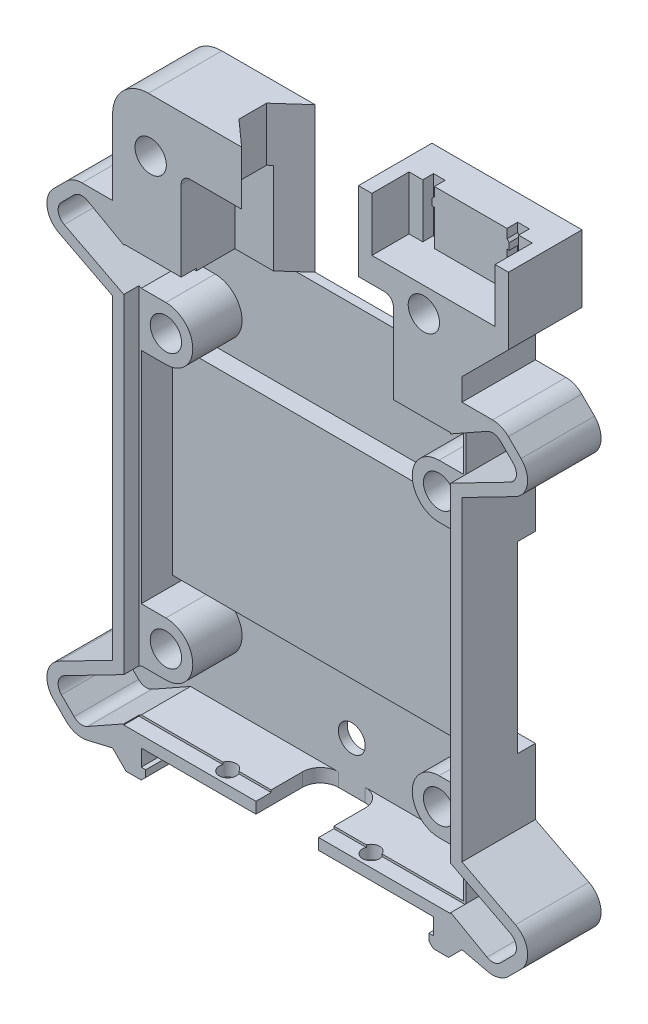
SolidWorks part; units mm, degrees
ref_plane "Front Plane" through (0, 0, 0) normal (0, 0, 1) x (1, 0, 0)
ref_plane "Top Plane" through (0, 0, 0) normal (0, 1, 0) x (1, 0, 0)
ref_plane "Right Plane" through (0, 0, 0) normal (1, 0, 0) x (0, 0, -1)
sketch "Sketch1" plane through (0, 0, 0) normal (0, 0, 1) x (1, 0, 0)
  line L0 (15.25, -20.35) -> (18, -20.35)
  line L1 (-19.5, -32.6) -> (19.5, -32.6)
  line L2 (-19.5, -32.6) -> (-19.5, 31.1)
  line L3 (-19.5, 31.1) -> (19.5, 31.1)
  line L4 (19.5, -32.6) -> (19.5, 31.1)
  line L5 (-15.25, -20.35) -> (-18, -20.35)
  line L6 (15.25, -26.35) -> (18, -26.35)
  line L7 (6.95, 31.1) -> (-15.5, 31.1) construction
  line L8 (-18, -31.1) -> (-18, 29.6)
  line L9 (-18, 29.6) -> (18, 29.6)
  line L10 (18, -31.1) -> (18, 29.6)
  line L11 (-18, -31.1) -> (18, -31.1)
  line L12 (-18, 14.9) -> (18, 14.9)
  line L13 (7.85, 14.9) -> (-4.95, 14.9) construction
  line L14 (-15.25, 4.15) -> (-18, 4.15)
  line L15 (-15.25, 10.15) -> (-18, 10.15)
  line L16 (15.25, 10.15) -> (18, 10.15)
  line L17 (15.25, 4.15) -> (18, 4.15)
  line L18 (-15.25, -26.35) -> (-18, -26.35)
  line L19 (19.5, -32.6) -> (19.5, -18.35) construction
  line L20 (-19.5, -32.6) -> (-19.5, -18.35) construction
  line L21 (19.5, -32.6) -> (-19.5, -32.6) construction
  line L22 (0, 31.1) -> (0, -32.6) construction
  line L23 (9.45, 26.9) -> (24.7, 26.9)
  line L24 (9.45, 26.9) -> (9.45, 33.9)
  line L25 (9.45, 33.9) -> (24.7, 33.9)
  line L26 (24.7, 26.9) -> (24.7, 33.9)
  line L27 (18, 29.6) -> (19.5, 31.1) construction
  line L28 (18.75, 30.35) -> (0, 30.35) construction
  line L29 (9.45, 26.9) -> (7.95, 26.9) construction
  line L30 (-7.95, 31.1) -> (7.95, 31.1)
  line L31 (-7.95, 31.1) -> (-7.95, 29.6)
  line L32 (-7.95, 29.6) -> (7.95, 29.6)
  line L33 (7.95, 31.1) -> (7.95, 29.6)
  line L34 (-7.95, 31.1) -> (7.95, 29.6) construction
  line L35 (-7.95, 29.6) -> (7.95, 31.1) construction
  line L36 (7.95, 26.9) -> (7.95, 29.6) construction
  line L37 (18, 29.6) -> (19.5, 29.6) construction
  line L38 (24.7, 26.4) -> (19.5, 21.2)
  line L39 (9.45, 33.9) -> (7.95, 33.9)
  line L40 (23.2, 33.9) -> (23.2, 26.9)
  line L41 (7.95, 33.9) -> (7.95, 31.1)
  line L42 (24.7, 30.4) -> (23.2, 30.4) construction
  line L43 (24.7, 26.9) -> (19.5, 26.9)
  line L44 (24.7, 26.9) -> (24.7, 26.4)
  line L45 (24.7, 26.4) -> (19.5, 26.4)
  line L46 (19.5, 26.9) -> (19.5, 26.4)
  circle A0 centre (15.25, -23.35) radius 1.75
  arc A1 (-15.5, 31.1) -> (-19.5, 27.1) centre (-15.5, 27.1) ccw construction
  circle A2 centre (15.25, -23.35) radius 3
  arc A3 (-15.5, 31.1) -> (-19.5, 27.1) centre (-15.5, 27.1) ccw
  arc A4 (-15.5, 29.6) -> (-18, 27.1) centre (-15.5, 27.1) ccw
  circle A6 centre (-15.25, -23.35) radius 1.75
  circle A7 centre (-15.25, -23.35) radius 1.75
  circle A8 centre (-15.25, 7.15) radius 1.75
  circle A9 centre (15.25, 7.15) radius 1.75
  circle A10 centre (15.25, 25.15) radius 1.75
  circle A11 centre (-15.25, 25.15) radius 1.75
  circle A12 centre (-15.25, -23.35) radius 3
  circle A13 centre (-15.25, -23.35) radius 3
  circle A14 centre (15.25, 7.15) radius 3
  circle A15 centre (-15.25, 7.15) radius 3
  dimension "D2" = 1.5
  dimension "D4" = 6
  dimension "D3" = 3.5
  dimension "D5" = 13.75
  dimension "D6" = 15.9
  dimension "D7" = 7
  dimension "D8" = 45
  dimension "D9" = 0.5
  dimension "D1" = 1.5
extrude "Base shape" add sketch "Sketch1" along normal up to surface (8.2 mm away) contours A15 L8 L9 L31 L3 A3 L2 L1 L4 L23 L10 A14 A2 L11 A12 | A12 L8 L18 | A12 L8 A6 | L8 A12 | A12 L5 L8 | A15 L8 L14 | A15 L8 A8 | L8 A15 | A15 L15 L8 | L23 A10 L24 L9 A4 L8 L12 L10 A11 | A4 L9 L8 | L33 L3 L31 L9 | L3 L33 L9 L24 | L24 L9 L10 L23 L4 L3 | L24 L23 L10 L9 | A14 L10 L16 | L10 A14 A9 | A14 L17 L10 | L10 A14 | L10 A2 L6 | A2 L10 A0 | L0 A2 L10 | A2 L10 | L40 L25 L24 L3 L4 L23 | L25 L40 L23 L26 | L38 L45 L4 | L45 L44 L23 L4 | L39 L41 L3 L24 region at (16.8481, -20.9099, 0) region at (17.3601, -20.8437, 0) region at (18.7469, -8.1, 0) region at (17.3601, -25.8563, 0) region at (18.1004, -23.35, 0) region at (17.3601, 4.6437, 0) region at (16.8481, 4.7099, 0) region at (18.1004, 7.15, 0) region at (17.3601, 9.6563, 0) region at (-17.3601, -25.8563, 0) region at (-0.6044, 21.831, 0) region at (-18.1004, -23.35, 0) region at (-17.9169, -23.35, 0) region at (13.725, 28.25, 0) region at (15.3803, 29.9053, 0) region at (-17.3601, -20.8437, 0) region at (22.1, 26.65, 0) region at (17.77, 31.4935, 0) region at (-17.3601, 9.6563, 0) region at (-17.4416, 29.0416, 0) region at (8.7, 30.35, 0) region at (21.2333, 24.6667, 0) region at (23.95, 30.4, 0) region at (-16.8481, 9.5901, 0) region at (-18.1004, 7.15, 0) region at (-17.3601, 4.6437, 0) region at (0, 30.35, 0) region at (8.7, 32.5, 0)
sketch "Sketch3" plane through (19.5, 0, 0) normal (1, 0, 0) x (0, 0, -1)
  line L1 (0, -18.35) -> (-2, -18.35)
  line L2 (0, -18.35) -> (0, 2.15)
  line L3 (0, 2.15) -> (-2, 2.15)
  line L4 (-2, -18.35) -> (-2, 2.15)
  line L5 (0, -18.35) -> (1.75, -18.35) construction
  line L6 (0, 2.15) -> (1.75, 2.15) construction
  line L7 (0, -32.6) -> (0, 21.2) construction
  dimension "D1" = 2
extrude "Strap cut" cut sketch "Sketch3" against normal through all
sketch "Sketch4" plane through (0, 31.1, 0) normal (0, 1, 0) x (1, 0, 0)
  line L2 (7.95, 0) -> (-5.0998, 0)
  line L4 (-15.5, 0) -> (7.95, 0) construction
  line L5 (-15.5, -8.2) -> (7.95, -8.2) construction
  line L6 (7.95, -8.2) -> (-5.0998, -8.2)
  line L12 (7.95, -8.3) -> (7.95, 0.1)
  line L13 (7.95, 0.1) -> (-4.9883, 0.1)
  line L14 (-4.9883, 0.1) -> (-7.95, -2.5553)
  line L15 (-7.95, -2.5553) -> (-7.95, -5.6447)
  line L16 (-7.95, -5.6447) -> (-4.9883, -8.3)
  line L17 (-4.9883, -8.3) -> (7.95, -8.3)
  line L18 (7.95, -8.3) -> (7.95, 0.1)
  line L19 (7.95, 0.1) -> (-4.9883, 0.1)
  line L20 (-4.9883, 0.1) -> (-7.95, -2.5553)
  line L21 (-7.95, -2.5553) -> (-7.95, -5.6447)
  line L22 (-7.95, -5.6447) -> (-4.9883, -8.3)
  line L23 (-4.9883, -8.3) -> (7.95, -8.3)
  dimension "D1" = 0.1
extrude "XT60 cut" cut sketch "Sketch4" against normal up to next contours L21 L22 L18 L20 region at (0.4142, 31.1, 4.1)
sketch "Sketch6" plane through (0, 0, 8.2) normal (0, 0, 1) x (1, 0, 0)
  line L0 (8.85, 14.9) -> (10.85, 14.9) construction
  line L1 (11.85, 24.1) -> (11.85, 15.9) construction
  line L3 (-11.85, 14.9) -> (11.85, 14.9)
  line L4 (-11.85, 24.1) -> (-11.85, 15.9) construction
  line L5 (11.85, 24.1) -> (11.85, 15.9)
  line L6 (10.85, 25.1) -> (-10.85, 25.1)
  line L7 (-11.85, 24.1) -> (-11.85, 15.9)
  line L8 (-11.85, 15.9) -> (-11.85, 14.9)
  line L9 (11.85, 15.9) -> (11.85, 14.9)
  arc A2 (-10.85, 25.1) -> (-11.85, 24.1) centre (-10.85, 24.1) ccw construction
  arc A3 (-10.85, 25.1) -> (-11.85, 24.1) centre (-10.85, 24.1) ccw
  arc A4 (11.85, 24.1) -> (10.85, 25.1) centre (10.85, 24.1) ccw construction
  arc A5 (11.85, 24.1) -> (10.85, 25.1) centre (10.85, 24.1) ccw
  line M1 (7.95, 33.9) -> (7.95, 14.9)
  line M15 (-5.0998, 14.9) -> (-5.0998, 31.1)
  line M118 (7.95, 14.9) -> (18, 14.9)
  line M134 (-18, 14.9) -> (-5.0998, 14.9)
extrude "IO wires cut" cut sketch "Sketch6" against normal blind 6 contours L7 L8 M134 M15 | L3 M15 M1 | L5 L9 M1 M118 region at (-8.465, 19.9848, 8.2) region at (1.4251, 20, 8.2) region at (9.8906, 19.9735, 8.2)
sketch "Sketch7" plane through (-18, 0, 0) normal (1, 0, 0) x (0, 0, -1)
  line L6 (0, -18.35) -> (0, -20.35)
  line L7 (-2, -18.35) -> (0, -18.35)
  line L8 (-2, 2.15) -> (-2, -18.35)
  line L9 (0, 2.15) -> (-2, 2.15)
  line L12 (0, 3.15) -> (-3, 3.15)
  line L13 (-3, 3.15) -> (-3, -19.35)
  line L14 (-3, -19.35) -> (-1, -19.35)
  line L15 (-1, -19.35) -> (-1, -20.35)
  line L16 (-1, -20.35) -> (0, -20.35)
  line L17 (0, 3.15) -> (-1, 3.15)
  line L19 (0, -31.1) -> (-1, -31.1)
  line L22 (0, -31.1) -> (0, -20.35)
  line L23 (0, -20.35) -> (-1, -20.35)
  line L24 (-1, -31.1) -> (-1, -20.35)
  line L25 (0, 3.15) -> (0, 14.9)
  line L26 (0, 14.9) -> (-1, 14.9)
  line L27 (-1, 3.15) -> (-1, 14.9)
  line L28 (-8.2, 14.9) -> (0, 14.9) construction
  line L31 (0, -20.35) -> (0, -18.35) construction
  line L32 (0, 2.15) -> (-2, 2.15) construction
  line M48 (0, -20.35) -> (0, -18.35)
  line M49 (0, -18.35) -> (-2, -18.35)
  line M50 (-2, -18.35) -> (-2, 2.15)
  line M51 (-2, 2.15) -> (0, 2.15)
  line M52 (0, 2.15) -> (0, 4.15)
  line M53 (0, 4.15) -> (-8.2, 4.15)
  line M55 (-8.2, -20.35) -> (0, -20.35)
  dimension "D1" = 1
extrude "Bottom" add sketch "Sketch7" along normal up to surface (36 mm away) contours L27 L25 L26 M53 | L27 L12 M52 M53 | L14 L15 L12 L13 M55 M48 M49 M50 M51 M52 | L24 L19 L22 M55 region at (-18, -8.5273, 2.2091) region at (-18, -25.725, 0.5) region at (-18, 3.65, 0.5) region at (-18, 9.525, 0.5) up to face at (18, -8.1, 2.55)
sketch "Sketch9" plane through (0, 0, 0) normal (0, 0, -1) x (-1, 0, 0)
  circle A0 centre (15.25, -23.35) radius 1.75 construction
  circle A1 centre (-15.25, 7.15) radius 1.75 construction
  circle A2 centre (15.25, 7.15) radius 1.75 construction
  circle A3 centre (15.25, -23.35) radius 1.75 construction
  circle A4 centre (15.25, -23.35) radius 1.75
  circle A5 centre (-15.25, 7.15) radius 1.75
  circle A6 centre (15.25, 7.15) radius 1.75
  circle A7 centre (15.25, -23.35) radius 1.75
  circle A8 centre (-15.25, -23.35) radius 1.75 construction
  circle A9 centre (-15.25, -23.35) radius 1.75
extrude "Bottom holes" cut sketch "Sketch9" against normal up to next contours A5 | A6 | A4 | A9 region at (-15.25, -23.35, 0) region at (15.25, 7.15, 0) region at (-15.25, 7.15, 0) region at (15.25, -23.35, 0)
sketch "Sketch8" plane through (0, 0, 8.2) normal (0, 0, 1) x (1, 0, 0)
  line L1 (-18, 14.9) -> (18, -31.1) construction
  line L3 (-18.25, -31.35) -> (18.25, -31.35)
  line L4 (-18.25, -31.35) -> (-18.25, 15.15)
  line L5 (-18.25, 15.15) -> (18.25, 15.15)
  line L6 (18.25, -31.35) -> (18.25, 15.15)
  line L7 (-18.25, -31.35) -> (18.25, 15.15) construction
  line L8 (-18.25, 15.15) -> (18.25, -31.35) construction
  line L10 (-18, 10.15) -> (-18, 14.9) construction
  line L11 (-18, 14.9) -> (-18.25, 14.9) construction
  line L12 (-18, 14.9) -> (-18, 15.15) construction
  point P2 (0, -8.1)
  dimension "D1" = 0.25
extrude "PCB cut" cut sketch "Sketch8" against normal blind 1.7
sketch "Sketch11" plane through (0, -32.6, 0) normal (0, -1, 0) x (1, 0, 0)
  line L1 (0, 8.2) -> (0, 0) construction
  line L2 (-19.5, 8.2) -> (19.5, 8.2) construction
  line L3 (-19.5, 0) -> (19.5, 0) construction
  line L4 (18, 1) -> (-18, 1) construction
  line L5 (-3.5, 8.2) -> (3.5, 8.2)
  line L6 (-3.5, 8.2) -> (-3.5, 3)
  line L7 (-1.5, 1) -> (1.5, 1)
  line L8 (3.5, 8.2) -> (3.5, 3)
  line L9 (-3.5, 8.2) -> (3.5, 1) construction
  line L10 (-3.5, 1) -> (3.5, 8.2) construction
  arc A0 (1.5, 1) -> (3.5, 3) centre (1.5, 3) ccw
  arc A1 (-3.5, 3) -> (-1.5, 1) centre (-1.5, 3) ccw
  point P7 (0, 4.6)
  line M5 (19.5, 8.2) -> (-19.5, 8.2)
  dimension "D2" = 2
  dimension "D1" = 7
extrude "Ledbar wires cut" cut sketch "Sketch11" against normal up to next contours L8 L6 L7 M5 region at (0, -32.6, 4.7112)
sketch "Sketch13" plane through (0, -32.6, 0) normal (0, -1, 0) x (1, 0, 0)
  line L0 (-19.5, 8.2) -> (-3.5, 8.2) construction
  line L1 (19.5, 0) -> (16.3, 0)
  line L2 (19.5, 0) -> (19.5, 8.2)
  line L3 (19.5, 8.2) -> (16.3, 8.2)
  line L4 (16.3, 0) -> (16.3, 8.2)
  line L5 (16.1, -1.8) -> (16.1, 8.2) construction
  line L6 (0, 8.2) -> (0, 0) construction
  line L7 (-19.5, 0) -> (-16.3, 0)
  line L8 (-19.5, 0) -> (-19.5, 8.2)
  line L9 (-19.5, 8.2) -> (-16.3, 8.2)
  line L10 (-16.3, 0) -> (-16.3, 8.2)
  line L11 (-3.5, 8.2) -> (3.5, 8.2) construction
  dimension "D1" = 0.2
extrude "Ledbar sides" add sketch "Sketch13" along normal blind 1.6
sketch "Sketch16" plane through (0, 33.9, 0) normal (0, 1, 0) x (1, 0, 0)
  line L0 (7.95, -6.125) -> (24.7, -6.125) construction
  line L1 (7.95, -8.2) -> (24.7, -8.2) construction
  line L2 (21.675, -2.85) -> (20.375, -2.85)
  line L3 (20.375, -4.05) -> (20.375, -2.85)
  line L4 (9.45, -4.05) -> (23.2, -4.05)
  line L5 (9.45, -4.05) -> (9.45, -8.2)
  line L6 (9.45, -8.2) -> (23.2, -8.2)
  line L7 (23.2, -4.05) -> (23.2, -8.2)
  line L8 (9.45, -4.05) -> (23.2, -8.2) construction
  line L9 (9.45, -8.2) -> (23.2, -4.05) construction
  line L10 (24.7, -8.2) -> (24.7, 0) construction
  line L11 (7.95, -8.2) -> (7.95, 0) construction
  line L12 (16.325, -8.2) -> (16.325, -4.05) construction
  line L13 (11.625, -2.85) -> (11.625, -4.05) construction
  line L14 (10.975, -4.05) -> (12.275, -4.05)
  line L15 (10.975, -4.05) -> (10.975, -2.85)
  line L16 (10.975, -2.85) -> (12.275, -2.85)
  line L17 (12.275, -4.05) -> (12.275, -2.85)
  line L18 (10.975, -2.85) -> (10.975, -8.2) construction
  line L19 (21.675, -4.05) -> (21.675, -2.85)
  point P6 (16.325, -6.125)
  dimension "D1" = 13.75
  dimension "D2" = 4.15
  dimension "D3" = 1.3
  dimension "D4" = 1.2
  dimension "D5" = 4.7
extrude "Balance plug cut" cut sketch "Sketch16" against normal blind 6 contours L7 L4 L5 L6 | L4 L17 L16 L15 | L4 L19 L2 L3 region at (21.025, 33.9, 3.45) region at (16.325, 33.9, 6.125) region at (11.625, 33.9, 3.45)
sketch "Sketch17" plane through (0, 0, 2.85) normal (0, 0, 1) x (1, 0, 0)
  line L0 (16.325, 33.9) -> (16.325, 27.9) construction
  line L1 (12.275, 33.9) -> (20.375, 33.9) construction
  line L2 (12.275, 27.9) -> (20.375, 27.9) construction
  line L3 (12.275, 27.9) -> (12.275, 33.9) construction
  line L4 (12.025, 32.9) -> (20.625, 32.9)
  line L5 (12.025, 32.9) -> (12.025, 31.9)
  line L6 (12.025, 31.9) -> (20.625, 31.9)
  line L7 (20.625, 32.9) -> (20.625, 31.9)
  line L8 (12.025, 32.9) -> (20.625, 31.9) construction
  line L9 (12.025, 31.9) -> (20.625, 32.9) construction
  line L10 (12.025, 32.65) -> (12.275, 32.9)
  line L11 (20.625, 32.65) -> (20.375, 32.9)
  point P6 (16.325, 32.4)
  line M7 (20.375, 33.9) -> (20.375, 27.9)
  dimension "D1" = 0.25
  dimension "D2" = 1
  dimension "D3" = 1
  dimension "D4" = 45
extrude "Balance plug locks" add sketch "Sketch17" along normal up to surface (1.2 mm away) contours L10 L5 L6 L4 M7 | L7 L11 L6 M7 region at (16.2154, 32.3984, 2.85) region at (20.494, 32.3405, 2.85) up to face at (16.325, 30.9, 4.05)
sketch "Sketch18" plane through (0, 0, 0) normal (0, 0, -1) x (-1, 0, 0)
  line L0 (0, -32.6) -> (0, -18.35) construction
  line L1 (16.3, -32.6) -> (-16.3, -32.6) construction
  line L2 (19.5, -18.35) -> (-19.5, -18.35) construction
  line L3 (-19.5, -28.6) -> (19.5, -28.6) construction
  line L4 (-19.5, -34.2) -> (-19.5, -18.35) construction
  line L5 (19.5, -34.2) -> (19.5, -18.35) construction
  circle A0 centre (0, -27.1) radius 1.5
  dimension "D2" = 3
  dimension "D1" = 4
extrude "PDB removal hole" cut sketch "Sketch18" against normal up to next
sketch "Sketch14" plane through (0, -32.6, 0) normal (0, -1, 0) x (1, 0, 0)
  circle A0 centre (8, 6.85) radius 0.95
  circle A1 centre (-8, 6.85) radius 0.95
  dimension "D1" = 1.9
extrude "Ledbar holes" cut sketch "Sketch14" against normal up to next
sketch "Sketch22" plane through (0, 0, 0) normal (0, 0, -1) x (-1, 0, 0)
  line L0 (22.918, 18.7322) -> (19.5, 18.7322)
  line L1 (19.5, -34.2) -> (19.5, 27.1) construction
  line L2 (19.5, -25.7166) -> (25.4771, -28.7956)
  line L3 (-23.4483, 13.9341) -> (-22.0341, 15.3483)
  line L4 (-23.8019, 17.1161) -> (-25.2161, 15.7019)
  line L5 (-23.4483, 13.9341) -> (-22.0341, 15.3483)
  line L6 (-23.8019, 17.1161) -> (-25.2161, 15.7019)
  line L7 (-22.5645, 13.0503) -> (-21.1503, 14.4645)
  line L8 (-25.2161, -31.9019) -> (-23.8019, -33.3161)
  line L9 (-22.0341, -31.5483) -> (-23.4483, -30.1341)
  line L10 (-25.2161, -31.9019) -> (-23.8019, -33.3161)
  line L11 (-22.0341, -31.5483) -> (-23.4483, -30.1341)
  line L12 (-24.6858, 18) -> (-26.1, 16.5858)
  line L13 (22.0341, 15.3483) -> (23.4483, 13.9341)
  line L14 (25.2161, 15.7019) -> (23.8019, 17.1161)
  line L15 (22.0341, 15.3483) -> (23.4483, 13.9341)
  line L16 (25.2161, 15.7019) -> (23.8019, 17.1161)
  line L17 (23.8019, -33.3161) -> (25.2161, -31.9019)
  line L18 (23.4483, -30.1341) -> (22.0341, -31.5483)
  line L19 (23.8019, -33.3161) -> (25.2161, -31.9019)
  line L20 (23.4483, -30.1341) -> (22.0341, -31.5483)
  line L21 (26.1, 16.5858) -> (24.6858, 18)
  line L22 (21.1503, 14.4645) -> (22.5645, 13.0503)
  line L23 (22.5645, -29.2503) -> (21.1503, -30.6645)
  line L24 (24.6858, -34.2) -> (26.1, -32.7858)
  line L25 (-21.1503, -30.6645) -> (-22.5645, -29.2503)
  line L26 (-26.1, -32.7858) -> (-24.6858, -34.2)
  line L27 (-19.5, 18.7322) -> (-22.918, 18.7322)
  line L28 (-19.5, -34.2) -> (-19.5, 21.2) construction
  line L29 (18, 10.15) -> (24.9047, 13.7068) construction
  line L30 (-19.5, -34.2) -> (-22.3484, -34.8665)
  line L31 (-19.5, -25.7166) -> (-25.4771, -28.7956)
  line L32 (19.5, 18.7322) -> (19.5, 9.5166)
  line L33 (19.5, -34.2) -> (22.3484, -34.8665)
  line L35 (24.9047, -29.9068) -> (18, -26.35) construction
  line L37 (-19.5, 9.5166) -> (-25.4771, 12.5956)
  line L38 (19.5, 9.5166) -> (25.4771, 12.5956)
  line L39 (-19.5, 18.7322) -> (-19.5, 9.5166)
  line L40 (-19.5, -25.7166) -> (-19.5, -34.2)
  line L41 (19.5, -25.7166) -> (19.5, -34.2)
  arc A0 (-26.1, 16.5858) -> (-22.5645, 13.0503) centre (-24.3322, 14.818) ccw
  arc A1 (-21.1503, 14.4645) -> (-24.6858, 18) centre (-22.918, 16.2322) ccw
  arc A2 (-22.0341, 15.3483) -> (-23.8019, 17.1161) centre (-22.918, 16.2322) ccw
  arc A3 (-25.2161, 15.7019) -> (-23.4483, 13.9341) centre (-24.3322, 14.818) ccw
  arc A4 (-22.0341, 15.3483) -> (-23.8019, 17.1161) centre (-22.918, 16.2322) ccw
  arc A5 (-25.2161, 15.7019) -> (-23.4483, 13.9341) centre (-24.3322, 14.818) ccw
  arc A6 (-23.4483, -30.1341) -> (-25.2161, -31.9019) centre (-24.3322, -31.018) ccw
  arc A7 (-23.8019, -33.3161) -> (-22.0341, -31.5483) centre (-22.918, -32.4322) ccw
  arc A8 (-23.4483, -30.1341) -> (-25.2161, -31.9019) centre (-24.3322, -31.018) ccw
  arc A9 (-23.8019, -33.3161) -> (-22.0341, -31.5483) centre (-22.918, -32.4322) ccw
  arc A10 (23.4483, 13.9341) -> (25.2161, 15.7019) centre (24.3322, 14.818) ccw
  arc A11 (23.8019, 17.1161) -> (22.0341, 15.3483) centre (22.918, 16.2322) ccw
  arc A12 (23.4483, 13.9341) -> (25.2161, 15.7019) centre (24.3322, 14.818) ccw
  arc A13 (23.8019, 17.1161) -> (22.0341, 15.3483) centre (22.918, 16.2322) ccw
  arc A14 (25.2161, -31.9019) -> (23.4483, -30.1341) centre (24.3322, -31.018) ccw
  arc A15 (22.0341, -31.5483) -> (23.8019, -33.3161) centre (22.918, -32.4322) ccw
  arc A16 (25.2161, -31.9019) -> (23.4483, -30.1341) centre (24.3322, -31.018) ccw
  arc A17 (22.0341, -31.5483) -> (23.8019, -33.3161) centre (22.918, -32.4322) ccw
  arc A18 (22.5645, 13.0503) -> (26.1, 16.5858) centre (24.3322, 14.818) ccw
  arc A19 (24.6858, 18) -> (21.1503, 14.4645) centre (22.918, 16.2322) ccw
  arc A20 (26.1, -32.7858) -> (22.5645, -29.2503) centre (24.3322, -31.018) ccw
  arc A21 (21.1503, -30.6645) -> (24.6858, -34.2) centre (22.918, -32.4322) ccw
  arc A22 (-24.6858, -34.2) -> (-21.1503, -30.6645) centre (-22.918, -32.4322) ccw
  arc A23 (-22.5645, -29.2503) -> (-26.1, -32.7858) centre (-24.3322, -31.018) ccw
  dimension "D1" = 0
  dimension "D2" = 0
  dimension "D3" = 0
  dimension "D4" = 0
  dimension "D5" = 1.25
extrude "ESC wire tunnels" add sketch "Sketch22" against normal up to surface (8.2 mm away) contours A19 L0 A18 L22 | L21 A19 L22 A18 A13 L16 A12 L15 | A1 L12 A0 L7 A5 L6 A4 L5 | A1 L7 A0 L27 | A21 L23 A20 L33 | L23 A21 L24 A20 A17 L20 A16 L19 | A23 L25 A22 L30 | L25 A23 L26 A22 A9 L10 A8 L11 | L16 A13 L15 A12 | L6 A5 L5 A4 | L10 A9 L11 A8 | L20 A17 L19 A16 region at (-20.9045, 13.5633, 0) region at (-23.84, 18.4581, 0) region at (-20.927, -29.4513, 0) region at (-26.7127, -30.6464, 0) region at (23.6251, 15.5251, 0) region at (23.9606, 12.4376, 0) region at (20.9045, 13.5633, 0) region at (23.6251, -31.7251, 0) region at (-23.6251, 15.5251, 0) region at (-23.6251, -31.7251, 0) region at (20.6011, -33.0929, 0) region at (20.927, -29.4513, 0) up to face at (17, 25.15, 8.2)
sketch "Sketch23" plane through (0, 0, 8.2) normal (0, 0, 1) x (1, 0, 0)
  line L46 (-18, 14.9) -> (-22.3052, 17.3217)
  line L47 (-18, 10.15) -> (-18.9276, 10.6278)
  line L48 (-18, 14.9) -> (-18, 10.15)
  line L49 (-18.9276, 10.6278) -> (-24.9047, 13.7068)
  line L50 (-25.2161, 15.7019) -> (-23.8019, 17.1161)
  line L51 (-22.918, 17.4822) -> (-19.5, 17.4822)
  line L52 (-18.9276, 10.6278) -> (-24.9047, 13.7068)
  line L53 (-25.2161, 15.7019) -> (-23.8019, 17.1161)
  line L54 (-22.918, 17.4822) -> (-19.5, 17.4822)
  line L58 (-18, -31.1) -> (-22.3052, -33.5217)
  line L59 (-18.9276, -26.8278) -> (-18, -26.35)
  line L60 (-18, -26.35) -> (-18, -31.1)
  line L61 (-22.6332, -33.6494) -> (-19.7848, -32.9829)
  line L62 (-25.2161, -31.9019) -> (-23.8019, -33.3161)
  line L63 (-18.9276, -26.8278) -> (-24.9047, -29.9068)
  line L64 (-22.6332, -33.6494) -> (-19.7848, -32.9829)
  line L65 (-25.2161, -31.9019) -> (-23.8019, -33.3161)
  line L66 (-18.9276, -26.8278) -> (-24.9047, -29.9068)
  line L67 (0, -6.351) -> (0, 7.9246) construction
  line L68 (18, -26.35) -> (18, -31.1)
  line L69 (18, -31.1) -> (22.3052, -33.5217)
  line L70 (25.2161, -31.9019) -> (23.8019, -33.3161)
  line L71 (18.9276, -26.8278) -> (24.9047, -29.9068)
  line L72 (18.9276, -26.8278) -> (18, -26.35)
  line L73 (18, 10.15) -> (18.9276, 10.6278)
  line L74 (18.9276, 10.6278) -> (24.9047, 13.7068)
  line L75 (25.2161, 15.7019) -> (23.8019, 17.1161)
  line L76 (18, 14.9) -> (22.3052, 17.3217)
  line L77 (18, 14.9) -> (18, 10.15)
  circle A30 centre (-22.918, 16.2322) radius 1.25
  arc A32 (-25.2161, 15.7019) -> (-24.9047, 13.7068) centre (-24.3322, 14.818) ccw
  arc A33 (-22.918, 17.4822) -> (-23.8019, 17.1161) centre (-22.918, 16.2322) ccw
  arc A34 (-25.2161, 15.7019) -> (-24.9047, 13.7068) centre (-24.3322, 14.818) ccw
  arc A35 (-22.918, 17.4822) -> (-23.8019, 17.1161) centre (-22.918, 16.2322) ccw
  circle A37 centre (-22.918, -32.4322) radius 1.25
  circle A38 centre (22.918, -32.4322) radius 1.25
  arc A39 (-23.8019, -33.3161) -> (-22.6332, -33.6494) centre (-22.918, -32.4322) ccw
  arc A40 (-24.9047, -29.9068) -> (-25.2161, -31.9019) centre (-24.3322, -31.018) ccw
  arc A41 (-23.8019, -33.3161) -> (-22.6332, -33.6494) centre (-22.918, -32.4322) ccw
  arc A42 (-24.9047, -29.9068) -> (-25.2161, -31.9019) centre (-24.3322, -31.018) ccw
  arc A43 (24.9047, -29.9068) -> (25.2161, -31.9019) centre (24.3322, -31.018) cw
  arc A44 (25.2161, 15.7019) -> (24.9047, 13.7068) centre (24.3322, 14.818) cw
  circle A45 centre (22.918, 16.2322) radius 1.25
  line M163 (18.25, 15.15) -> (18.25, -31.35)
  dimension "D1" = 1.25
  dimension "D2" = 1.25
extrude "Wire tunnel cuts" cut sketch "Sketch23" against normal up to surface (7.2 mm away) contours A30 | L53 A34 L52 L47 L48 L46 A30 | A45 | L75 A45 L76 L73 L74 A44 M163 | A38 | A43 L71 L72 L69 A38 L70 M163 | A37 | L66 A42 L65 A37 L58 L60 L59 region at (-21.1189, 13.7975, 8.2) region at (-22.918, 16.2322, 8.2) region at (-21.1189, -29.9975, 8.2) region at (-22.918, -32.4322, 8.2) region at (21.2543, 13.852, 8.2) region at (21.2543, -30.052, 8.2) region at (22.918, -32.4322, 8.2) region at (22.918, 16.2322, 8.2) up to face at (0.1239, 8.7929, 1)
sketch "Sketch24" plane through (0, 0, 8.2) normal (0, 0, 1) x (1, 0, 0)
  line L0 (0, -4.5098) -> (0, 6.2776) construction
  line L1 (-16.3, -34.2) -> (-19.5, -34.2) construction
  line L2 (19.5, -35.7) -> (-19.5, -35.7)
  line L3 (19.5, -35.7) -> (19.5, -34.2)
  line L4 (19.5, -34.2) -> (-19.5, -34.2)
  line L5 (-19.5, -35.7) -> (-19.5, -34.2)
  line L6 (19.5, -35.7) -> (-19.5, -34.2) construction
  line L7 (19.5, -34.2) -> (-19.5, -35.7) construction
  line L8 (-16.3, -34.2) -> (-16.3, -32.6) construction
  line L9 (-16.3, -34.2) -> (-16.3, -35.7)
  line L10 (15.8, -35.7) -> (-15.8, -35.7)
  line L11 (15.8, -35.7) -> (15.8, -34.2)
  line L12 (15.8, -34.2) -> (-15.8, -34.2)
  line L13 (-15.8, -35.7) -> (-15.8, -34.2)
  line L14 (15.8, -35.7) -> (-15.8, -34.2) construction
  line L15 (15.8, -34.2) -> (-15.8, -35.7) construction
  line L16 (-19.5, -34.2) -> (-18, -35.7)
  line L17 (-15.8, -34.45) -> (-16.3, -34.45)
  line L18 (-15.8, -34.45) -> (-15.8, -35.2)
  line L19 (-15.8, -35.2) -> (-16.3, -35.7)
  line L20 (16.3, -34.2) -> (16.3, -35.7)
  line L21 (15.8, -34.45) -> (16.3, -34.45)
  line L22 (15.8, -35.7) -> (15.8, -34.2)
  line L23 (15.8, -35.2) -> (16.3, -35.7)
  line L24 (19.5, -34.2) -> (18, -35.7)
  point P1 (0, -34.95)
  point P12 (0, -34.95)
  dimension "D1" = 1.5
  dimension "D2" = 0.25
  dimension "D3" = 0.5
  dimension "D4" = 0.75
  dimension "D5" = 45
extrude "Ledbar holders" add sketch "Sketch24" against normal up to surface (8.2 mm away) contours L19 L9 L4 L16 L2 | L19 L13 L17 L9 | L24 L4 L20 L23 L2 | L22 L23 L20 L21 region at (17.5633, -34.8735, 8.2) region at (16.0708, -34.9604, 8.2) region at (-17.5633, -34.8735, 8.2) region at (-16.0708, -34.9604, 8.2) up to face at (-1.5, -27.1, 0)
sketch "Sketch10" plane through (0, 0, 2) normal (0, 0, -1) x (-1, 0, 0)
  line L0 (0, 2.15) -> (0, -18.35) construction
  line L1 (19.5, 2.15) -> (-19.5, 2.15) construction
  line L2 (19.5, -18.35) -> (-19.5, -18.35) construction
  line L3 (19.5, 2.15) -> (19.5, -18.35) construction
  line L4 (-19.5, 1.15) -> (19.5, 1.15)
  line L5 (-19.5, 1.15) -> (-19.5, 0.65)
  line L6 (-19.5, 0.65) -> (19.5, 0.65)
  line L7 (19.5, 1.15) -> (19.5, 0.65)
  line L8 (-19.5, 1.15) -> (19.5, 0.65) construction
  line L9 (-19.5, 0.65) -> (19.5, 1.15) construction
  line L10 (-19.5, 2.15) -> (19.5, 2.15) construction
  line L11 (-19.5, -1.35) -> (19.5, -1.35)
  line L12 (19.5, -0.85) -> (19.5, -1.35)
  line L13 (-19.5, -0.85) -> (19.5, -0.85)
  line L14 (-19.5, -0.85) -> (-19.5, -1.35)
  line L15 (-19.5, -3.35) -> (19.5, -3.35)
  line L16 (19.5, -2.85) -> (19.5, -3.35)
  line L17 (-19.5, -2.85) -> (19.5, -2.85)
  line L18 (-19.5, -2.85) -> (-19.5, -3.35)
  line L19 (-19.5, -5.35) -> (19.5, -5.35)
  line L20 (19.5, -4.85) -> (19.5, -5.35)
  line L21 (-19.5, -4.85) -> (19.5, -4.85)
  line L22 (-19.5, -4.85) -> (-19.5, -5.35)
  line L23 (-19.5, -7.35) -> (19.5, -7.35)
  line L24 (19.5, -6.85) -> (19.5, -7.35)
  line L25 (-19.5, -6.85) -> (19.5, -6.85)
  line L26 (-19.5, -6.85) -> (-19.5, -7.35)
  line L27 (-19.5, -9.35) -> (19.5, -9.35)
  line L28 (19.5, -8.85) -> (19.5, -9.35)
  line L29 (-19.5, -8.85) -> (19.5, -8.85)
  line L30 (-19.5, -8.85) -> (-19.5, -9.35)
  line L31 (-19.5, -11.35) -> (19.5, -11.35)
  line L32 (19.5, -10.85) -> (19.5, -11.35)
  line L33 (-19.5, -10.85) -> (19.5, -10.85)
  line L34 (-19.5, -10.85) -> (-19.5, -11.35)
  line L35 (-19.5, -13.35) -> (19.5, -13.35)
  line L36 (19.5, -12.85) -> (19.5, -13.35)
  line L37 (-19.5, -12.85) -> (19.5, -12.85)
  line L38 (-19.5, -12.85) -> (-19.5, -13.35)
  line L39 (-19.5, -15.35) -> (19.5, -15.35)
  line L40 (19.5, -14.85) -> (19.5, -15.35)
  line L41 (-19.5, -14.85) -> (19.5, -14.85)
  line L42 (-19.5, -14.85) -> (-19.5, -15.35)
  line L43 (-19.5, -17.35) -> (19.5, -17.35)
  line L44 (19.5, -16.85) -> (19.5, -17.35)
  line L45 (-19.5, -16.85) -> (19.5, -16.85)
  line L46 (-19.5, -16.85) -> (-19.5, -17.35)
  point P6 (0, 0.9)
  dimension "D1" = 1
  dimension "D2" = 0.5
  dimension "D4" = 2
  dimension "D3" = 10
extrude "3D print ribs" [suppressed] add sketch "Sketch10" along normal up to surface (2 mm away) up to face at (-17, 7.15, 0)
